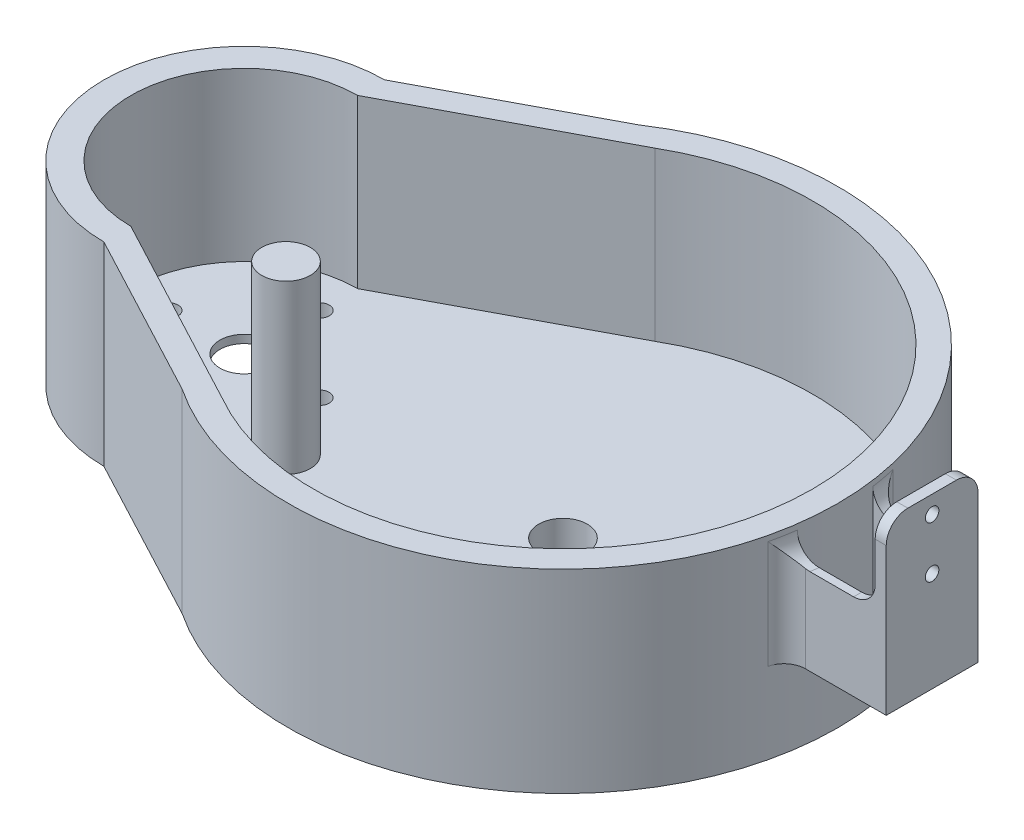
SolidWorks part; units mm, degrees
note: The reader was unsure of these and kept them because the rebuilt part matched: shared geometry of "Sketch3<10>", "Sketch2<6>", "Sketch2<7>", "Sketch8<3>", "Sketch3<13>".
ref_plane "Front Plane" through (0, 0, 0) normal (0, 0, 1) x (1, 0, 0)
ref_plane "Top Plane" through (0, 0, 0) normal (0, 1, 0) x (1, 0, 0)
ref_plane "Right Plane" through (0, 0, 0) normal (1, 0, 0) x (0, 0, -1)
sketch "Sketch2" plane through (0, 0, 0) normal (0, 1, 0) x (1, 0, 0)
  line L0 (0, 26) -> (30.8523, 42.3604)
  line L1 (0, -26) -> (30.8523, -42.3604)
  line L2 (0, 21) -> (33.849, 36.7093)
  line L3 (0, -21) -> (30.8523, -34.4606)
  line L4 (109.945, 0) -> (123.335, 0)
  line L5 (123.335, 0) -> (123.335, 4)
  line L6 (123.335, 4) -> (109.7876, 4)
  line L7 (123.335, 0) -> (123.335, -4)
  line L8 (123.335, -4) -> (109.7876, -4)
  line L9 (-26, 0) -> (-39.6319, 0)
  line L10 (-39.6319, 0) -> (-39.6319, 4)
  line L11 (-39.6319, 4) -> (-25.6905, 4)
  line L12 (-39.6319, 0) -> (-39.6319, -4)
  line L13 (-39.6319, -4) -> (-25.6905, -4)
  line L14 (-39.6319, 0) -> (-42.7319, 0)
  line L15 (123.335, 0) -> (127.435, 0)
  line L16 (127.435, 0) -> (127.435, 8.5)
  line L17 (127.435, 8.5) -> (109.2301, 8.5)
  line L18 (127.435, 0) -> (127.435, -8.5)
  line L19 (127.435, -8.5) -> (109.2301, -8.5)
  line L20 (125.385, 0) -> (125.385, 7)
  line L21 (125.385, 7) -> (109.4613, 7)
  line L22 (125.385, 0) -> (125.385, -7)
  line L23 (125.385, -7) -> (109.4613, -7)
  line L24 (123.335, -4) -> (123.335, 0)
  circle A1 centre (59.055, 0) radius 44.53
  circle A2 centre (0, 0) radius 4.5
  circle A3 centre (59.055, 0) radius 4.5
  circle A5 centre (59.055, 0) radius 50.89
  arc A6 (0, -26) -> (0, 26) centre (0, 0) cw
  arc A7 (0, 21) -> (0, -21) centre (0, 0) ccw
  circle A8 centre (121.085, 0) radius 1.75
  circle A9 centre (-37.3819, 0) radius 1.75
  dimension "D1" = 59.055
  dimension "D2" = 101.78
  dimension "D3" = 89.06
  dimension "D4" = 26
  dimension "D5" = 30.8523
  dimension "D7" = 101.78
  dimension "D8" = 2.25
  dimension "D9" = 2.25
  dimension "D6" = 30.8523
extrude "Boss-Extrude1" add sketch "Sketch2" along normal blind 5
sketch "Sketch3" plane through (0, 5, 0) normal (0, 1, 0) x (1, 0, 0)
  line L0 (0, 26) -> (30.8523, 42.3604)
  line L1 (0, -26) -> (30.8523, -42.3604)
  line L2 (0, 21) -> (35.9898, 40.0847)
  line L3 (0, -21) -> (35.9898, -40.0847)
  line L5 (0, -22) -> (22, -22)
  line L6 (22, -22) -> (22, 22)
  line L7 (22, 22) -> (-22, 22)
  line L8 (-22, 22) -> (-22, -22)
  line L9 (-22, -22) -> (0, -22)
  line L10 (22, 22) -> (102, 22)
  line L11 (102, 22) -> (102, -22)
  line L12 (102, -22) -> (22, -22)
  line L13 (0, 26) -> (30.8523, 42.3604)
  line L14 (0, -26) -> (30.8523, -42.3604)
  circle A1 centre (59.055, 0) radius 50.89
  circle A3 centre (59.055, 0) radius 46.247
  arc A4 (0, 26) -> (0, -26) centre (0, 0) ccw
  arc A5 (0, -26) -> (0, 26) centre (0, 0) cw
  arc A6 (0, 21) -> (0, -21) centre (0, 0) ccw
  arc A7 (0, 26) -> (0, -26) centre (0, 0) ccw construction
  circle A9 centre (20, -12.2608) radius 4.5
  dimension "D1" = 0
  dimension "D3" = 20
  dimension "D2" = 44
  dimension "D4" = 12.2608
extrude "Boss-Extrude4" add sketch "Sketch3" along normal blind 31
extrude "Boss-Extrude5" add sketch "Sketch3<10>" along normal blind 31 contours A3 L11 L10 | A3 L12 L11
sketch "Sketch3<10>" plane through (0, 5, 0) normal (0, 1, 0) x (1, 0, 0) same geometry as "Sketch3"
extrude "Boss-Extrude6" add sketch "Sketch2<6>" along normal blind 31 contours A5 L21 L20 L15 L16 L17 | A5 L19 L18 L15 L22 L23
sketch "Sketch2<6>" plane through (0, 0, 0) normal (0, 1, 0) x (1, 0, 0) same geometry as "Sketch2"
sketch "Sketch5" plane through (0, 31, 0) normal (0, 1, 0) x (1, 0, 0)
  line L0 (127.435, 8.5) -> (127.435, -8.5)
  line L1 (127.435, -8.5) -> (125.385, -8.5)
  line L2 (127.435, -8.5) -> (109.2301, -8.5) construction
  line L3 (125.385, -8.5) -> (125.385, 8.5)
  line L4 (127.435, 8.5) -> (109.2301, 8.5) construction
  line L5 (125.385, 8.5) -> (127.435, 8.5)
extrude "Boss-Extrude7" add sketch "Sketch5" along normal blind 15.25
sketch "Sketch6" plane through (127.435, 0, 0) normal (1, 0, 0) x (0, 0, -1)
  line L0 (0, 46.25) -> (0, 0)
  line L1 (-8.5, 46.25) -> (8.5, 46.25) construction
  circle A0 centre (0, 43) radius 1.25
  circle A1 centre (0, 33.5) radius 1.25
  dimension "D1" = 9.5
  dimension "D2" = 3.25
extrude "Cut-Extrude3" cut sketch "Sketch6" against normal blind 5 contours L0 A0 | L0 A0 | L0 A1 | L0 A1
extrude "Cut-Extrude4" cut sketch "Sketch2<7>" along normal blind 15 contours A5 L19 L18 L15 L22 L23 | A5 L21 L20 L15 L16 L17
sketch "Sketch2<7>" plane through (0, 0, 0) normal (0, 1, 0) x (1, 0, 0) same geometry as "Sketch2"
fillet "Fillet2" radius 4 8 edges at (126.41, 46.25, -8.5) (126.41, 46.25, 8.5) (125.385, 31, -7.75) (125.385, 31, 7.75) (109.2301, 23, -8.5) (109.2301, 23, 8.5) (109.3513, 31, -7.7509) (109.3513, 31, 7.7509)
sketch "Sketch8" plane through (0, 0, 0) normal (0, -1, 0) x (1, 0, 0)
  circle A0 centre (0, 0) radius 14
  circle A1 centre (0, 14) radius 1.75
  circle A2 centre (14, 0) radius 1.75
  circle A3 centre (0, -14) radius 1.75
  circle A4 centre (-14, 0) radius 1.75
  circle A5 centre (0, 0) radius 11.5
  circle M6 centre (0, 0) radius 4.5
extrude "Cut-Extrude5" cut sketch "Sketch8" against normal blind 10 contours A1 | A2 | A3 | A4
extrude "Cut-Extrude6" cut sketch "Sketch8<3>" against normal blind 3.5 contours A5 M6
sketch "Sketch8<3>" plane through (0, 0, 0) normal (0, -1, 0) x (1, 0, 0) same geometry as "Sketch8"
extrude "Boss-Extrude8" add sketch "Sketch3<13>" along normal blind 31 contours L6 A9 | L6 A9
sketch "Sketch3<13>" plane through (0, 5, 0) normal (0, 1, 0) x (1, 0, 0) same geometry as "Sketch3"
